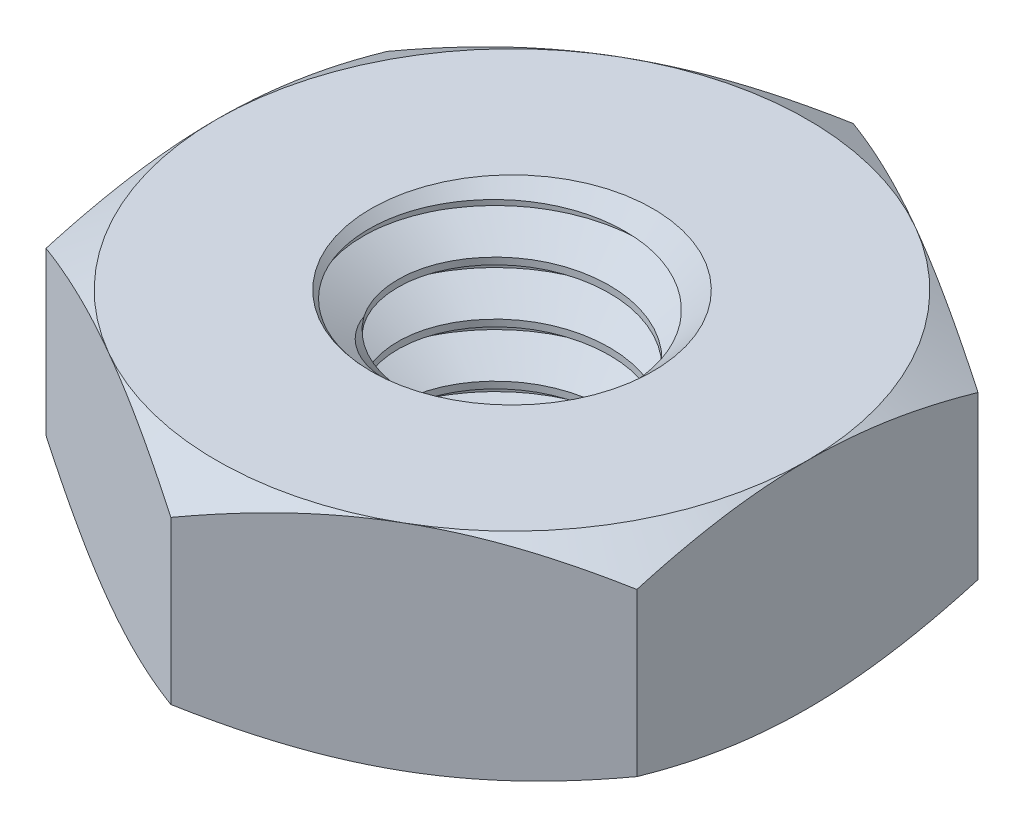
SolidWorks part; units mm, degrees
ref_plane "Front Plane" through (0, 0, 0) normal (0, 0, 1) x (1, 0, 0)
ref_plane "Top Plane" through (0, 0, 0) normal (0, 1, 0) x (1, 0, 0)
ref_plane "Right Plane" through (0, 0, 0) normal (1, 0, 0) x (0, 0, -1)
sketch "Sketch7" plane through (0, 0, 0) normal (0, 1, 0) x (1, 0, 0)
  line L0 (-4.3656, 0) -> (4.3656, 0) construction
  line L1 (-2.0828, 0) -> (2.0828, 0) construction
  line L2 (-4.3656, 0) -> (-4.3656, -0.7937) construction
  point P4 (0, 0)
  point P8 (0, 0)
sketch "Sketch6" plane through (0, 0, 0) normal (1, 0, 0) x (0, 0, -1)
  line L0 (0, 1.5875) -> (0, -1.5875) construction
  point P4 (0, 0)
sketch "Sketch1" plane through (0, 0, 0) normal (0, 1, 0) x (1, 0, 0)
  line L1 (-4.3656, 2.5205) -> (-4.3656, -2.5205)
  line L2 (-4.3656, -2.5205) -> (0, -5.041)
  line L3 (0, -5.041) -> (4.3656, -2.5205)
  line L4 (4.3656, -2.5205) -> (4.3656, 2.5205)
  line L5 (4.3656, 2.5205) -> (0, 5.041)
  line L6 (0, 5.041) -> (-4.3656, 2.5205)
  circle A0 centre (0, 0) radius 4.3656 construction
  circle A1 centre (0, 0) radius 2.0828
extrude "Boss-Extrude1" add sketch "Sketch1" along normal mid plane 3.175
sketch "Sketch5" plane through (0, 1.5875, 0) normal (0, 1, 0) x (1, 0, 0)
  circle A0 centre (0, 0) radius 4.3656 construction
  circle A1 centre (0, 0) radius 4.3656
extrude "Cut-Extrude2" cut sketch "Sketch5" against normal through all draft 60 flip side to cut
mirror "Mirror1" about plane through (0, 0, 0) normal (0, 1, 0) of "Cut-Extrude2"
sketch "Sketch14" plane through (0, 1.5875, 0) normal (0, 1, 0) x (1, 0, 0)
  line L0 (-2.0828, 0) -> (2.0828, 0) construction
  line L1 (0, 2.0828) -> (0, -2.0828) construction
  circle A0 centre (0, 0) radius 2.0828 construction
  point P7 (0, 0)
  point P11 (0, 0)
  point P12 (0, -2.0828)
  point P13 (-2.0828, 0)
  point P14 (0, 2.0828)
  point P15 (2.0828, 0)
sketch "Sketch8" plane through (0, 1.5875, 0) normal (0, 1, 0) x (1, 0, 0)
  circle A0 centre (0, 0) radius 2.0828 construction
  circle A1 centre (0, 0) radius 2.0828
extrude "Boss-Extrude2" add sketch "Sketch8" against normal up to surface (3.175 mm away) separate body up to face at (0, -1.5875, 0)
sketch "Sketch9" plane through (0, 1.5875, 0) normal (0, 1, 0) x (1, 0, 0)
  circle A0 centre (0, 0) radius 2.0828 construction
  circle A1 centre (0, 0) radius 2.0828
extrude "Boss-Extrude3" add sketch "Sketch9" against normal up to surface (3.175 mm away) up to face at (0, -1.5875, 0)
sketch "Sketch10" plane through (0, 1.5875, 0) normal (0, 1, 0) x (1, 0, 0)
  circle A0 centre (0, 0) radius 2.0828 construction
  circle A1 centre (0, 0) radius 2.0828
curve "Helix/Spiral1" pitch 0.7937 height 3.9688 radius 2.0828 centre (0, 1.5875, 0) axis (0, -1, 0) start towards (0, 0, 1)
sketch "Sketch11" plane through (0, 0, 0) normal (1, 0, 0) x (0, 0, -1)
  line L0 (-2.0828, 1.5875) -> (-2.0828, 2.282)
  line L1 (2.0828, 1.5875) -> (-2.0828, 1.5875) construction
  line L2 (-2.0828, 2.282) -> (-1.5672, 1.9844)
  line L3 (-1.5672, 1.9844) -> (-1.5672, 1.8852)
  line L4 (-1.5672, 1.8852) -> (-2.0828, 1.5875)
  line L5 (-2.0828, 1.9348) -> (-1.5672, 1.9348) construction
  line L6 (-1.825, 2.1332) -> (-1.825, 1.7363) construction
  spline S0 degree 3 poles (-2.0828, 1.5875) (-2.0828, 1.5711) (-1.9744, 1.5378) (-1.5111, 1.4883) (-0.8178, 1.4387) (0, 1.3891) (0.8178, 1.3395) (1.5111, 1.2898) (1.9744, 1.2402) (2.137, 1.1906) (1.9744, 1.141) (1.5111, 1.0914) (0.8178, 1.0418) (0, 0.9922) (-0.8178, 0.9426) (-1.5111, 0.893) (-1.9744, 0.8434) (-2.137, 0.7938) (-1.9744, 0.7441) (-1.5111, 0.6945) (-0.8178, 0.6449) (0, 0.5953) (0.8178, 0.5457) (1.5111, 0.4961) (1.9744, 0.4465) (2.137, 0.3969) (1.9744, 0.3473) (1.5111, 0.2977) (0.8178, 0.248) (0, 0.1984) (-0.8178, 0.1488) (-1.5111, 0.0992) (-1.9744, 0.0496) (-2.137, 0) (-1.9744, -0.0496) (-1.5111, -0.0992) (-0.8178, -0.1488) (0, -0.1984) (0.8178, -0.248) (1.5111, -0.2977) (1.9744, -0.3473) (2.137, -0.3969) (1.9744, -0.4465) (1.5111, -0.4961) (0.8178, -0.5457) (0, -0.5953) (-0.8178, -0.6449) (-1.5111, -0.6945) (-1.9744, -0.7441) (-2.137, -0.7938) (-1.9744, -0.8434) (-1.5111, -0.893) (-0.8178, -0.9426) (0, -0.9922) (0.8178, -1.0418) (1.5111, -1.0914) (1.9744, -1.141) (2.137, -1.1906) (1.9744, -1.2402) (1.5111, -1.2898) (0.8178, -1.3395) (0, -1.3891) (-0.8178, -1.4387) (-1.5111, -1.4883) (-1.9744, -1.5379) (-2.137, -1.5875) (-1.9744, -1.6371) (-1.5111, -1.6867) (-0.8178, -1.7363) (0, -1.7859) (0.8178, -1.8355) (1.5111, -1.8852) (1.9744, -1.9348) (2.137, -1.9844) (1.9744, -2.034) (1.5111, -2.0836) (0.8178, -2.1332) (0, -2.1828) (-0.8178, -2.2324) (-1.5111, -2.282) (-1.9744, -2.3316) (-2.0828, -2.3648) (-2.0828, -2.3813) knots 0 0 0 0 0.0125 0.025 0.0375 0.05 0.0625 0.075 0.0875 0.1 0.1125 0.125 0.1375 0.15 0.1625 0.175 0.1875 0.2 0.2125 0.225 0.2375 0.25 0.2625 0.275 0.2875 0.3 0.3125 0.325 0.3375 0.35 0.3625 0.375 0.3875 0.4 0.4125 0.425 0.4375 0.45 0.4625 0.475 0.4875 0.5 0.5125 0.525 0.5375 0.55 0.5625 0.575 0.5875 0.6 0.6125 0.625 0.6375 0.65 0.6625 0.675 0.6875 0.7 0.7125 0.725 0.7375 0.75 0.7625 0.775 0.7875 0.8 0.8125 0.825 0.8375 0.85 0.8625 0.875 0.8875 0.9 0.9125 0.925 0.9375 0.95 0.9625 0.975 0.9875 1 1 1 1 construction
  dimension "D1" = 60
  dimension "D2" = 0.0992
  dimension "D3" = 0.3969
sweep "Cut-Sweep1" cut profiles "Sketch11" path "Helix/Spiral1" align with end faces yes
combine bodies "Combine1" operation type subtract main body 107 bodies to subtract 108
sketch "Sketch12" plane through (0, 1.5875, 0) normal (0, 1, 0) x (1, 0, 0)
  circle A1 centre (0, 0) radius 2.0828
  circle A2 centre (0, 0) radius 2.0828
  dimension "D1" = 0
extrude "Cut-Extrude3" cut sketch "Sketch12" against normal through all draft 45
sketch "Sketch13" plane through (0, -1.5875, 0) normal (0, -1, 0) x (1, 0, 0)
  circle A1 centre (0, 0) radius 2.0828
  circle A2 centre (0, 0) radius 2.0828
  dimension "D1" = 0
extrude "Cut-Extrude4" cut sketch "Sketch13" against normal through all draft 45
equation "\"D3@Helix/Spiral1\"=\"Thickness@Sketch6\"+\"Pitch@Sketch7\""
equation "\"Height@Boss-Extrude1\"=\"Thickness@Sketch6\""
equation "\"D4@Helix/Spiral1\"=\"Pitch@Sketch7\""
equation "\"D2@Sketch11\"=\"Pitch@Sketch7\"*.125"
equation "\"D3@Sketch11\"=\"Pitch@Sketch7\"*.5"
